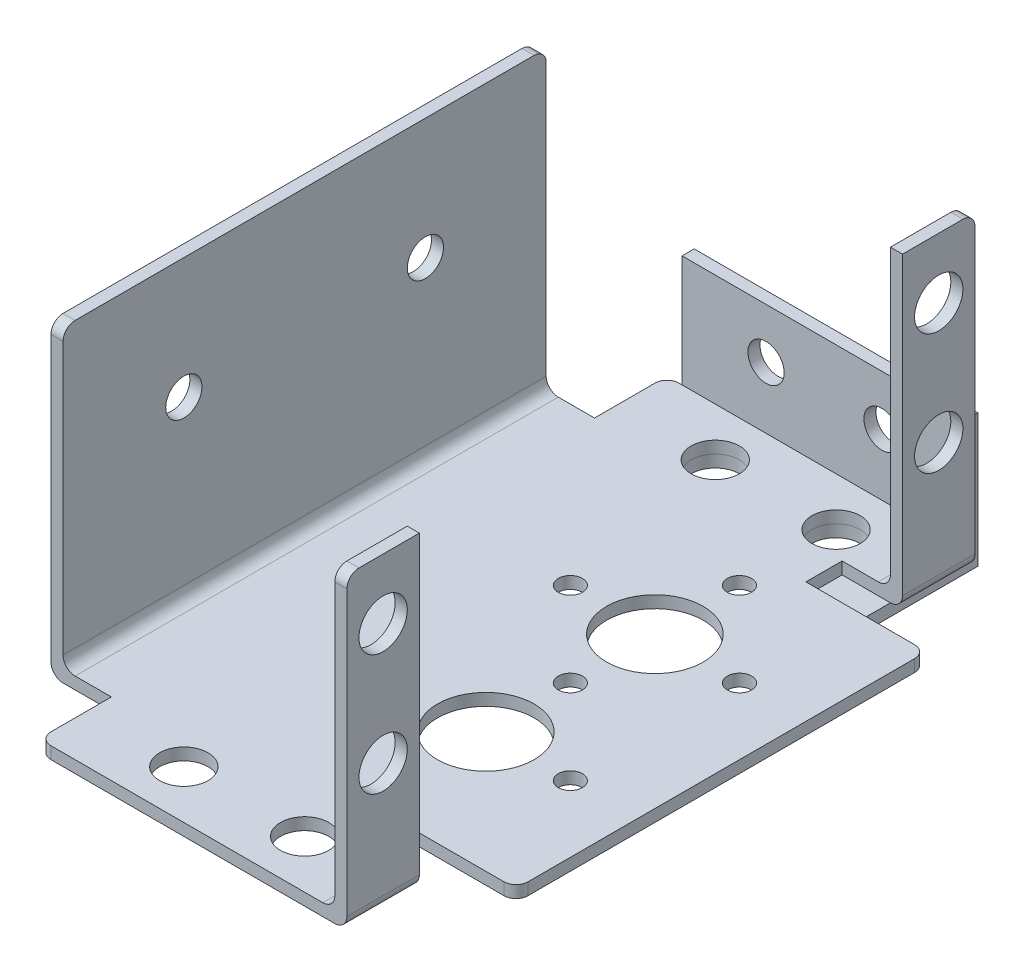
SolidWorks part; units mm, degrees
ref_plane "Front" through (0, 0, 0) normal (0, 0, 1) x (1, 0, 0)
ref_plane "Top" through (0, 0, 0) normal (0, 1, 0) x (1, 0, 0)
ref_plane "Right" through (0, 0, 0) normal (1, 0, 0) x (0, 0, -1)
sketch "Sketch1" plane through (0, 0, 0) normal (0, 0, 1) x (1, 0, 0)
  line L0 (-0.5, 25) -> (0.5, 25)
  line L1 (35, 0.5) -> (35, -0.5)
  line L2 (1.5, 0.5) -> (35, 0.5)
  line L3 (0.5, 1.5) -> (0.5, 25)
  line L4 (0.5, -0.5) -> (35, -0.5)
  line L5 (-0.5, 0.5) -> (-0.5, 25)
  arc A0 (0.5, 1.5) -> (1.5, 0.5) centre (1.5, 1.5) ccw
  arc A1 (-0.5, 0.5) -> (0.5, -0.5) centre (0.5, 0.5) ccw
extrude "Boss-Extrude1" add sketch "Sketch1" against normal blind 52
sketch "Sketch2" plane through (0, -0.5, 0) normal (0, -1, 0) x (1, 0, 0)
  circle A0 centre (22.5, -19) radius 4
  circle A1 centre (22.5, -33) radius 4
  circle A2 centre (22.5, -26) radius 1
  circle A3 centre (15.5, -19) radius 1
  circle A4 centre (22.5, -12) radius 1
  circle A5 centre (29.5, -19) radius 1
  circle A6 centre (29.5, -33) radius 1
  circle A7 centre (22.5, -40) radius 1
  circle A8 centre (15.5, -33) radius 1
  circle A9 centre (22.5, -4) radius 2
  circle A10 centre (22.5, -48) radius 2
  circle A11 centre (12.5, -48) radius 2
  circle A12 centre (12.5, -4) radius 2
  point P15 (22.5, -19)
  point P22 (22.5, -33)
extrude "Cut-Extrude1" cut sketch "Sketch2" against normal through all
sketch "Sketch3" plane through (-0.5, 0, 0) normal (-1, 0, 0) x (0, 0, 1)
  line L1 (-52, 25) -> (0, 25) construction
  line L2 (-6, 25) -> (-6, -0.5)
  line L3 (-52, -0.5) -> (-46, -0.5)
  line L5 (-52, 25) -> (-52, -0.5)
  line L6 (-6, 25) -> (0, 25)
  line L7 (0, 25) -> (0, -0.5)
  line L8 (0, -0.5) -> (-6, -0.5)
  line L9 (-46, 25) -> (-52, 25)
  line L10 (-46, 25) -> (-46, -0.5)
  circle A0 centre (-16, 15) radius 1.5
  circle A1 centre (-36, 15) radius 1.5
extrude "Cut-Extrude3" cut sketch "Sketch3" against normal blind 5
sketch "Sketch4" plane through (0, 0.5, 0) normal (0, 1, 0) x (1, 0, 0)
  line L0 (30, 46) -> (25, 46)
  line L1 (35, 52) -> (35, 0) construction
  line L2 (25, 46) -> (25, 43)
  line L3 (25, 43) -> (35, 43)
  line L5 (30, 46) -> (30, 52)
  line L6 (35, 52) -> (4.5, 52) construction
  line L7 (30, 6) -> (30, 0)
  line L8 (25, 9) -> (35, 9)
  line L9 (25, 6) -> (25, 9)
  line L10 (30, 6) -> (25, 6)
  line M5 (4.5, 0) -> (35, 0)
  line M6 (35, 0) -> (35, 52)
  line M7 (35, 52) -> (4.5, 52)
extrude "Cut-Extrude4" cut sketch "Sketch4" against normal through all contours L5 L0 L2 L3 M6 M7 | L10 L7 L8 L9 M5 M6 region at (31.25, 0.5, -46.75) region at (31.25, 0.5, -5.25)
sketch "Sketch5" plane through (0, 0.5, 0) normal (0, 1, 0) x (1, 0, 0)
  line L0 (30, 52) -> (30, 46)
  line L1 (30, 46) -> (29, 46)
  line L3 (29, 46) -> (29, 52)
  line L4 (30, 52) -> (4.5, 52) construction
  line L5 (29, 52) -> (30, 52)
  line L8 (29, 0) -> (30, 0)
  line L9 (29, 6) -> (29, 0)
  line L10 (30, 6) -> (29, 6)
  line L11 (30, 0) -> (30, 6)
extrude "Boss-Extrude2" add sketch "Sketch5" along normal up to surface (24.5 mm away) up to face at (0, 25, -26)
fillet "Fillet1" radius 1 4 edges at (29, 0.5, -49) (30, -0.5, -49) (30, -0.5, -3) (29, 0.5, -3)
sketch "Sketch6" plane through (30, 0, 0) normal (1, 0, 0) x (0, 0, -1)
  circle A0 centre (3, 20) radius 2
  circle A1 centre (3, 10) radius 2
  circle A2 centre (49, 10) radius 2
  circle A3 centre (49, 20) radius 2
extrude "Cut-Extrude5" cut sketch "Sketch6" against normal blind 5
fillet "Fillet2" radius 1 8 edges at (4.5, 0, -52) (35, 0, -43) (35, 0, -9) (4.5, 0, 0) (0, 25, -6) (0, 25, -46) (29.5, 25, -52) (29.5, 25, 0)
sketch "Sketch7" plane through (0, -0.5, 0) normal (0, -1, 0) x (1, 0, 0)
  line L0 (29, -53.25) -> (29, -42)
  line L1 (5.5, -53.25) -> (29, -53.25)
  line L2 (5.5, -53.25) -> (5.5, -42)
  line L3 (5.5, -42) -> (29, -42)
  circle A0 centre (12.5, -48) radius 2
  circle A1 centre (22.5, -48) radius 2
extrude "Boss-Extrude7" add sketch "Sketch7" along normal blind 1 separate body
sketch "Sketch8" plane through (0, -0.5, 0) normal (0, 1, 0) x (1, 0, 0)
  line L0 (29, 53.25) -> (29, 42) construction
  line L1 (5.5, 53.25) -> (29, 53.25)
  line L2 (5.5, 53.25) -> (5.5, 52.25)
  line L3 (5.5, 52.25) -> (29, 52.25)
  line L4 (29, 53.25) -> (29, 52.25)
extrude "Boss-Extrude8" add sketch "Sketch8" along normal blind 10
sketch "Sketch9" plane through (0, 0, -52.25) normal (0, 0, 1) x (1, 0, 0)
  circle A0 centre (22.05, 5.3391) radius 1.5
  circle A3 centre (12.45, 5.3391) radius 1.5
extrude "Cut-Extrude6" cut sketch "Sketch9" against normal through all
